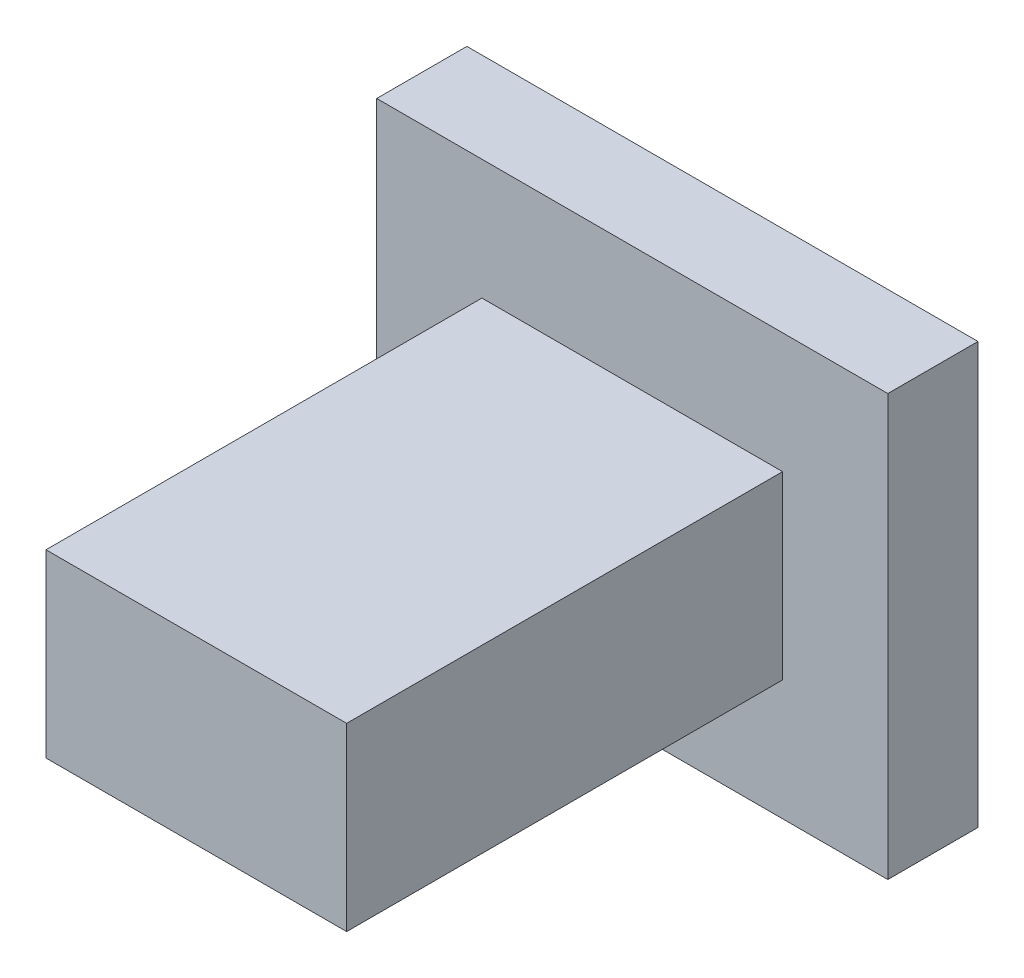
SolidWorks part; units mm, degrees
ref_plane "Front Plane" through (0, 0, 0) normal (0, 0, 1) x (1, 0, 0)
ref_plane "Top Plane" through (0, 0, 0) normal (0, 1, 0) x (1, 0, 0)
ref_plane "Right Plane" through (0, 0, 0) normal (1, 0, 0) x (0, 0, -1)
sketch "Sketch1" plane through (0, 0, 0) normal (0, 0, 1) x (1, 0, 0)
  line L0 (0, 1.5) -> (-1.75, 1.5) construction
  line L1 (0, 0) -> (5, 0)
  line L2 (0, 0) -> (0, 3)
  line L3 (0, 3) -> (5, 3)
  line L4 (5, 0) -> (5, 3)
  line L5 (-1.75, -2) -> (6.75, -2)
  line L6 (-1.75, -2) -> (-1.75, 5)
  line L7 (-1.75, 5) -> (6.75, 5)
  line L8 (6.75, -2) -> (6.75, 5)
  line L9 (2.5, 5) -> (2.5, 3) construction
  line L10 (6.75, 1.5) -> (5, 1.5) construction
  line L11 (2.5, 0) -> (2.5, -2) construction
  line L13 (0, 2.175) -> (1.35, 2.175)
  line L14 (0, 2.175) -> (0, 0.825)
  line L15 (0, 0.825) -> (1.35, 0.825)
  line L16 (1.35, 2.175) -> (1.35, 0.825)
  line L17 (2.5, 3) -> (2.5, 2.175) construction
  line L18 (1.35, 1.5) -> (5, 1.5) construction
  line L19 (2.5, 0.825) -> (2.5, 0) construction
  dimension "D1" = 5
  dimension "D2" = 3
  dimension "D3" = 2
  dimension "D4" = 1.75
  dimension "D5" = 1.35
  dimension "D6" = 1.75
extrude "Boss-Extrude1" add sketch "Sketch1" along normal blind 1.5 contours L5 L8 L7 L6 L4 L1 L2 L3 region at (-1.6399, 1.5, 0)
extrude "Boss-Extrude2" add sketch "Sketch1<3>" along normal blind 2.25 contours L1 L4 L3 L2 L16 L13 L14 L15 region at (2.7524, 1.5, 0)
sketch "Sketch1<3>" plane through (0, 0, 0) normal (0, 0, 1) x (1, 0, 0) same geometry as "Sketch1"
sketch "Sketch3" plane through (0, 0, 2.25) normal (0, 0, 1) x (1, 0, 0)
  line L1 (5, 3) -> (0, 3)
  line L2 (5, 3) -> (5, 0)
  line L3 (5, 0) -> (0, 0)
  line L4 (0, 3) -> (0, 0)
extrude "Boss-Extrude3" add sketch "Sketch3" along normal blind 6.5
